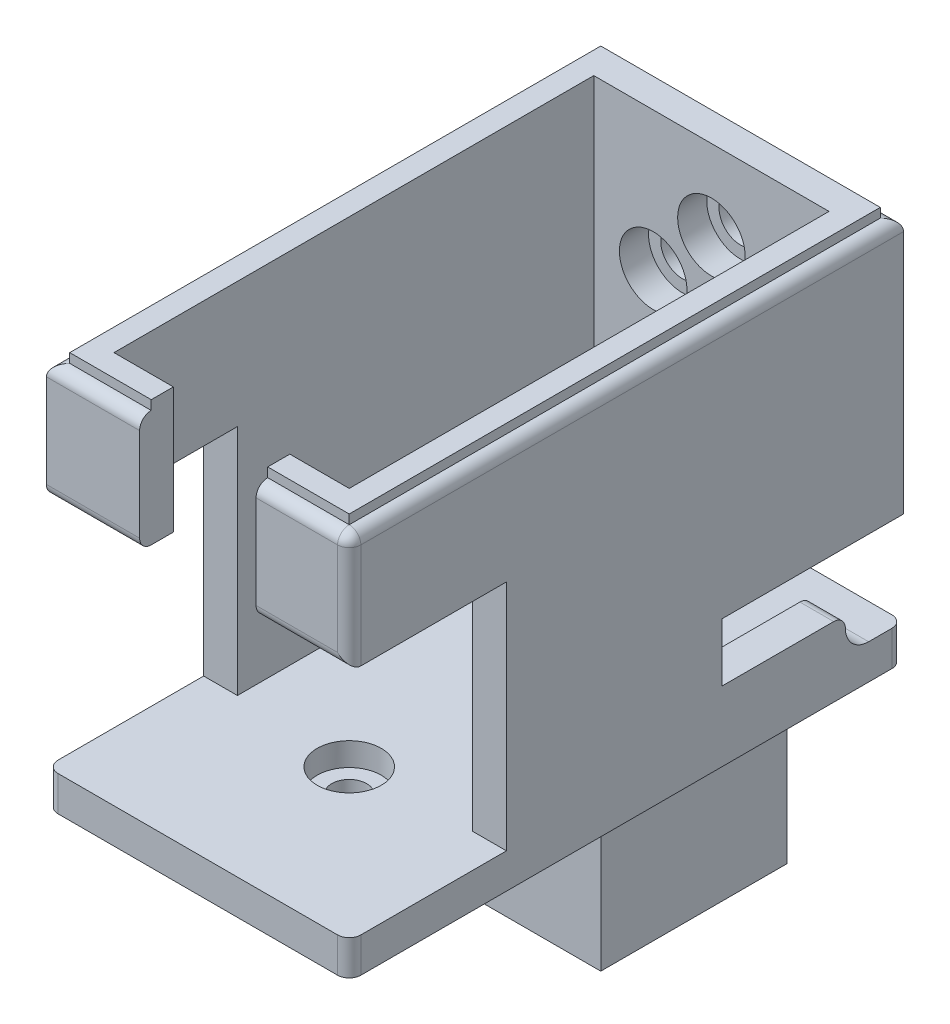
SolidWorks part; units mm, degrees
other "Markup1"
sketch "Sketch34" plane through (-13, 10, 23.5) normal (-0.1734, 0.635, 0.7528) x (0.9767, 0.2093, 0.0485)
ref_plane "Front Plane" through (0, 0, 0) normal (0, 0, 1) x (1, 0, 0)
ref_plane "Top Plane" through (0, 0, 0) normal (0, 1, 0) x (1, 0, 0)
ref_plane "Right Plane" through (0, 0, 0) normal (1, 0, 0) x (0, 0, -1)
sketch "Sketch1" plane through (0, 0, 0) normal (0, 1, 0) x (1, 0, 0)
  line L0 (5, -23.5) -> (13, -23.5)
  line L1 (-10, 20.5) -> (10, 20.5)
  line L2 (-10, 20.5) -> (-10, -20.5)
  line L3 (-10, -20.5) -> (-5, -20.5)
  line L4 (10, 20.5) -> (10, -20.5)
  line L5 (-10, 20.5) -> (10, -20.5) construction
  line L6 (-10, -20.5) -> (10, 20.5) construction
  line L7 (-13, 23.5) -> (13, 23.5)
  line L8 (-13, 23.5) -> (-13, -23.5)
  line L9 (-13, -23.5) -> (-5, -23.5)
  line L10 (13, 23.5) -> (13, -23.5)
  line L11 (-13, 23.5) -> (13, -23.5) construction
  line L12 (-13, -23.5) -> (13, 23.5) construction
  line L14 (-5, -20.5) -> (-5, -23.5)
  line L16 (5, -20.5) -> (5, -23.5)
  line L17 (5, -20.5) -> (10, -20.5)
  point P0 (0, 0)
  point P6 (0, 0)
  dimension "D1" = 20
  dimension "D2" = 41
  dimension "D3" = 3
  dimension "D4" = 3
  dimension "D5" = 5
  dimension "D6" = 5
extrude "Boss-Extrude1" add sketch "Sketch1" along normal blind 10
sketch "Sketch2" plane through (13, 0, 0) normal (1, 0, 0) x (0, 0, -1)
  line L0 (-23.5, 0) -> (23.5, 0) construction
  line L1 (-10, 0) -> (10, 0)
  line L2 (-10, 0) -> (-10, -17)
  line L3 (-10, -17) -> (10, -17)
  line L4 (10, 0) -> (10, -17)
  dimension "D1" = 10
  dimension "D2" = 10
  dimension "D3" = 17
extrude "Boss-Extrude2" add sketch "Sketch2" against normal blind 3
ref_plane "Plane1" through (0, 0, 0) normal (1, 0, 0) x (0, 0, -1)
mirror "Mirror1" about plane through (0, 0, 0) normal (1, 0, 0) of "Boss-Extrude2"
sketch "Sketch3" plane through (0, -17, 0) normal (0, -1, 0) x (1, 0, 0)
  line L1 (-13, 23.5) -> (13, 23.5)
  line L2 (-13, 23.5) -> (-13, -23.5)
  line L3 (-13, -23.5) -> (13, -23.5)
  line L4 (13, 23.5) -> (13, -23.5)
extrude "Boss-Extrude3" add sketch "Sketch3" along normal blind 3
sketch "Sketch5" plane through (0, -20, 0) normal (0, -1, 0) x (1, 0, 0)
  line L1 (10, 20.5) -> (5, 20.5) construction
  line L2 (10, 10) -> (10, -10) construction
  line L3 (-10, 10) -> (-10, -10) construction
  line L4 (-8, -4.5) -> (8, -4.5)
  line L5 (-8, -4.5) -> (-8, -8.5)
  line L6 (-8, -8.5) -> (8, -8.5)
  line L7 (8, -4.5) -> (8, -8.5)
  line L8 (-8, -12.5) -> (8, -12.5)
  line L9 (-8, -12.5) -> (-8, -16.5)
  line L10 (-8, -16.5) -> (8, -16.5)
  line L11 (8, -12.5) -> (8, -16.5)
  line L12 (-10, -10) -> (-10, -20.5) construction
  line L13 (10, -20.5) -> (10, -10) construction
  line L14 (-10, -20.5) -> (10, -20.5) construction
  circle A0 centre (0, 10.5) radius 8
  dimension "D1" = 10
  dimension "D2" = 10
  dimension "D3" = 2
  dimension "D4" = 2
  dimension "D5" = 2
  dimension "D6" = 2
  dimension "D7" = 4
  dimension "D8" = 4
  dimension "D9" = 4
  dimension "D10" = 4
extrude "Cut-Extrude1" cut sketch "Sketch5" against normal through all
sketch "Sketch6" plane through (13, 0, 0) normal (1, 0, 0) x (0, 0, -1)
  line L0 (23.5, -20) -> (23.5, 20.7) construction
  line L1 (23.5, -20) -> (-23.5422, -20) construction
  line L2 (23.5, -20) -> (23.5, 20.7) construction
  line L3 (23.5, 20.7) -> (-23.5422, 20.7) construction
  line L4 (-23.5422, -20) -> (-23.5422, 20.7) construction
  line L5 (23.5, -20) -> (23.5, 20.7) construction
  line L6 (23.5, 0.35) -> (-23.5422, 0.35) construction
  line L7 (10, -17) -> (10, 0) construction
  line L8 (23.5, 4.35) -> (29.5, 4.35)
  line L9 (23.5, 4.35) -> (23.5, -3.65)
  line L10 (23.5, -3.65) -> (29.5, -3.65)
  line L11 (29.5, 4.35) -> (29.5, -3.65)
  line L12 (23.5, 0) -> (10, 0)
  line L13 (23.5, 0) -> (23.5, -9.3)
  line L14 (23.5, -9.3) -> (10, -9.3)
  line L15 (10, 0) -> (10, -9.3)
  line M19 (10, -17) -> (10, 0)
  line M20 (10, 0) -> (23.5, 0)
  line M21 (23.5, 0) -> (23.5, 10)
  dimension "D1" = 40.7
  dimension "D2" = 4
  dimension "D3" = 4
  dimension "D4" = 6
  dimension "D5" = 5.65
extrude "Boss-Extrude4" add sketch "Sketch6" against normal blind 26 contours L11 L8 L9 L10 M21 | L14 L13 L9 M20 M19 region at (13, 0.35, -26.5) region at (13, -4.65, -16.75)
sketch "Sketch7" plane through (0, 0, 0) normal (0, 1, 0) x (1, 0, 0)
  line L1 (-10, 20.5) -> (10, 20.5)
  line L2 (-10, 20.5) -> (-10, 10)
  line L3 (-10, 10) -> (10, 10)
  line L4 (10, 20.5) -> (10, 10)
extrude "Cut-Extrude2" cut sketch "Sketch7" against normal blind 10
sketch "Sketch9" plane through (0, 4.35, 0) normal (0, 1, 0) x (1, 0, 0)
  line L0 (13, 23.5) -> (-13, 23.5) construction
  line L1 (-13, 29.5) -> (-5, 29.5)
  line L2 (-13, 29.5) -> (-13, 23.5)
  line L3 (-13, 23.5) -> (-5, 23.5)
  line L4 (-5, 29.5) -> (-5, 23.5)
  line L5 (-13, 23.5) -> (13, 23.5) construction
  line L6 (13, 29.5) -> (5, 29.5)
  line L7 (13, 29.5) -> (13, 23.5)
  line L8 (13, 23.5) -> (5, 23.5)
  line L9 (5, 29.5) -> (5, 23.5)
  dimension "D1" = 8
  dimension "D2" = 8
extrude "Cut-Extrude3" cut sketch "Sketch9" against normal blind 10
sketch "Sketch10" plane through (0, 0, -29.5) normal (0, 0, -1) x (-1, 0, 0)
  line L1 (-15, 15) -> (15, 15)
  line L2 (-15, 15) -> (-15, -15)
  line L3 (-15, -15) -> (15, -15)
  line L4 (15, 15) -> (15, -15)
  line L5 (-15, 15) -> (15, -15) construction
  line L6 (-15, -15) -> (15, 15) construction
  point P0 (0, 0)
  dimension "D1" = 30
  dimension "D2" = 30
extrude "Boss-Extrude5" add sketch "Sketch10" along normal blind 3
sketch "Sketch11" plane through (0, 0, -32.5) normal (0, 0, -1) x (-1, 0, 0)
  circle A0 centre (0, 10) radius 1.75
  circle A4 centre (10, 0) radius 1.75
  circle A5 centre (0, -10) radius 1.75
  circle A6 centre (-10, 0) radius 1.75
  point P12 (-1, 1)
  point P13 (0, 0)
  dimension "D1" = 3.5
  dimension "D3" = 0
  dimension "D4" = 4
  dimension "D5" = 10
  dimension "D6" = 10
  dimension "D2" = 10
extrude "Cut-Extrude4" cut sketch "Sketch11" against normal blind 5
sketch "Sketch12" plane through (0, -20, 0) normal (0, -1, 0) x (1, 0, 0)
  line L9 (-13, 23.5) -> (13, 23.5)
  line L10 (-13, 23.5) -> (-13, -23.5)
  line L11 (-13, -23.5) -> (13, -23.5)
  line L12 (13, 23.5) -> (13, -23.5)
  circle A0 centre (0, 10.5) radius 8
extrude "Boss-Extrude6" add sketch "Sketch12" along normal blind 3
sketch "Sketch14" plane through (0, -17, 0) normal (0, 1, 0) x (1, 0, 0)
  line L1 (-13, 23.5) -> (13, 23.5)
  line L2 (-13, 23.5) -> (-13, -23.5)
  line L3 (-13, -23.5) -> (13, -23.5)
  line L4 (13, 23.5) -> (13, -23.5)
  line L5 (-13, 10) -> (-10, 10)
  line L6 (-13, 10) -> (-13, -10)
  line L7 (-13, -10) -> (-10, -10)
  line L8 (-10, 10) -> (-10, -10)
  line L9 (10, -10) -> (13, -10)
  line L10 (10, -10) -> (10, 10)
  line L11 (10, 10) -> (13, 10)
  line L12 (13, -10) -> (13, 10)
  circle M1 centre (0, -10.5) radius 8
  line M2 (8, 4.5) -> (-8, 4.5)
  line M3 (-8, 4.5) -> (-8, 8.5)
  line M4 (-8, 8.5) -> (8, 8.5)
  line M5 (8, 8.5) -> (8, 4.5)
  line M6 (8, 12.5) -> (-8, 12.5)
  line M7 (-8, 12.5) -> (-8, 16.5)
  line M8 (-8, 16.5) -> (8, 16.5)
  line M9 (8, 16.5) -> (8, 12.5)
  line M10 (13, -10) -> (10, -10)
  line M11 (10, -10) -> (10, 10)
  line M12 (10, 10) -> (13, 10)
  line M13 (13, 10) -> (13, 23.5)
  line M14 (13, 23.5) -> (-13, 23.5)
  line M15 (-13, 23.5) -> (-13, 10)
  line M16 (-13, 10) -> (-10, 10)
  line M17 (-10, 10) -> (-10, -10)
  line M18 (-10, -10) -> (-13, -10)
  line M19 (-13, -10) -> (-13, -23.5)
  line M20 (-13, -23.5) -> (13, -23.5)
  line M21 (13, -23.5) -> (13, -10)
extrude "Cut-Extrude5" cut sketch "Sketch14" against normal blind 3 contours M21 M10 M11 M12 M13 M14 M15 M16 M17 M18 M19 M20 M5 M2 M3 M4 M9 M6 M7 M8 M1 region at (0, -17, -0.9925)
sketch "Sketch15" plane through (13, 0, 0) normal (1, 0, 0) x (0, 0, -1)
  line L0 (10, -20) -> (23.5, -20) construction
  line L1 (23.5, -17) -> (-23.5, -17)
  line L2 (23.5, -17) -> (23.5, 20.7)
  line L3 (23.5, 20.7) -> (-23.5, 20.7)
  line L4 (-23.5, -17) -> (-23.5, 20.7)
  line L5 (23.5, -23) -> (-23.5, -23) construction
  line L6 (11.2985, 20.7) -> (11.2985, -23) construction
  line L7 (11.2985, -23) -> (11.2985, -1.15) construction
  line L8 (11.2985, -1.15) -> (42.746, -1.15) construction
  line L10 (32.5, 15) -> (23.5, 15)
  line L11 (32.5, 15) -> (32.5, -15.2438)
  line L12 (32.5, -15.2438) -> (23.5, -15.2438)
  line L13 (23.5, 15) -> (23.5, -15.2438)
  line M11 (23.5, -9.3) -> (23.5, 10)
  dimension "D1" = 3
  dimension "D2" = 43.7
extrude "Cut-Extrude7" cut sketch "Sketch15" against normal through all both and the other way through all contours L12 L11 L10 L2 M11 region at (13, -0.1219, -28)
sketch "Sketch16" plane through (0, -9.3, 0) normal (0, -1, 0) x (1, 0, 0)
  line L0 (-13, 23.5) -> (-13, -23.5) construction
  line L1 (13, -23.5) -> (-13, -23.5)
  line L2 (13, -23.5) -> (13, -10)
  line L3 (13, -10) -> (-13, -10)
  line L4 (-13, -23.5) -> (-13, -10)
  line L5 (10, -10) -> (13, -10) construction
  line L7 (10, -20.5) -> (-10, -20.5)
  line L8 (10, -20.5) -> (10, -10)
  line L9 (10, -10) -> (-10, -10)
  line L10 (-10, -20.5) -> (-10, -10)
  line M2 (10, -20.5) -> (-10, -20.5)
  line M3 (-10, -20.5) -> (-10, -10)
  line M4 (-10, -10) -> (-13, -10)
  line M5 (-13, -10) -> (-13, -23.5)
  line M6 (-13, -23.5) -> (13, -23.5)
  line M7 (13, -23.5) -> (13, -10)
  line M8 (13, -10) -> (10, -10)
  line M9 (10, -10) -> (10, -20.5)
  dimension "D1" = 0
extrude "Boss-Extrude7" add sketch "Sketch16" along normal blind 10.7 contours M9 M2 M3 M4 M5 M6 M7 M8 region at (0, -9.3, -23.207)
sketch "Sketch18" plane through (13, 0, 0) normal (1, 0, 0) x (0, 0, -1)
  line L0 (23.5, 10) -> (23.5, -23) construction
  line L1 (23.5, -17) -> (8.5, -17)
  line L2 (23.5, -17) -> (23.5, -12)
  line L3 (23.5, -12) -> (8.5, -12)
  line L4 (8.5, -17) -> (8.5, -12)
  line L5 (-23.5, -20) -> (-10, -20) construction
  dimension "D1" = 3
  dimension "D2" = 15
  dimension "D3" = 5
extrude "Cut-Extrude8" cut sketch "Sketch18" against normal blind 10
mirror "Mirror2" about plane through (0, 0, 0) normal (1, 0, 0) of "Cut-Extrude8"
sketch "Sketch21" plane through (0, 0, -23.5) normal (0, 0, -1) x (-1, 0, 0)
  line L0 (0, 20.7) -> (0, -23) construction
  line L1 (-13, -23) -> (13, -23)
  line L2 (-13, -23) -> (-13, 20.7)
  line L3 (-13, 20.7) -> (13, 20.7)
  line L4 (13, -23) -> (13, 20.7)
  line L5 (0, -23) -> (0, -1.15) construction
  line L6 (0, -1.15) -> (13, -1.15) construction
  circle A0 centre (0, 3.85) radius 1.85
  circle A1 centre (5, -1.15) radius 1.85
  circle A2 centre (0, -6.15) radius 1.85
  circle A3 centre (-5, -1.15) radius 1.85
  point P19 (0, -1.15)
  dimension "D2" = 5
  dimension "D3" = 3.7
  dimension "D5" = 5
  dimension "D6" = 5
  dimension "D1" = 43.7
  dimension "D4" = 4
extrude "Cut-Extrude9" cut sketch "Sketch21" against normal blind 5 contours A3 | A0 | A1 | A2 region at (0, 3.85, -23.5) region at (-5, -1.15, -23.5) region at (0, -6.15, -23.5) region at (5, -1.15, -23.5)
sketch "Sketch22" plane through (0, 0, -20.5) normal (0, 0, 1) x (1, 0, 0)
  line L0 (0, 3.85) -> (0, -6.15) construction
  line L1 (0, -6.15) -> (0, -1.15) construction
  line L2 (0, -1.15) -> (5, -1.15) construction
  circle A0 centre (0, 3.85) radius 2.9
  circle A1 centre (5, -1.15) radius 2.9
  circle A2 centre (0, -6.15) radius 2.9
  circle A3 centre (-5, -1.15) radius 2.9
  point P17 (0, -1.15)
  dimension "D1" = 5.8
  dimension "D2" = 4
extrude "Cut-Extrude10" cut sketch "Sketch22" against normal blind 2.6
sketch "Sketch23" plane through (0, 0, -23.5) normal (0, 0, -1) x (-1, 0, 0)
  line L0 (-3, -17) -> (-13, -17)
  line L1 (-13, 10) -> (13, 10)
  line L2 (-13, 10) -> (-13, -12)
  line L3 (-13, -12) -> (-3, -12)
  line L4 (13, 10) -> (13, -12)
  line L10 (-3, -12) -> (-3, -17)
  line L12 (3, -12) -> (3, -17)
  line L13 (13, -17) -> (3, -17)
  line L14 (13, -17) -> (13, -23)
  line L15 (13, -23) -> (-13, -23)
  line L16 (-13, -17) -> (-13, -23)
  line L17 (3, -12) -> (13, -12)
  circle A0 centre (0, 3.85) radius 1.75
  circle A1 centre (0, -6.15) radius 1.75
  circle A2 centre (5, -1.15) radius 1.75
  circle A3 centre (-5, -1.15) radius 1.75
  circle M1 centre (-5, -1.15) radius 1.85
  circle M2 centre (0, 3.85) radius 1.85
  circle M3 centre (5, -1.15) radius 1.85
  circle M4 centre (0, -6.15) radius 1.85
  line M5 (3, -12) -> (13, -12)
  line M6 (13, -12) -> (13, 10)
  line M7 (13, 10) -> (-13, 10)
  line M8 (-13, 10) -> (-13, -12)
  line M9 (-13, -12) -> (-3, -12)
extrude "Boss-Extrude11" add sketch "Sketch23" along normal blind 0.6 contours L3 M9 M5 M6 M7 M8 M2 M4 M3 M1 region at (2.5799, -14.5, -23.5)
sketch "Sketch24" plane through (0, 0, -24.1) normal (0, 0, -1) x (-1, 0, 0)
  line L5 (5, -1.15) -> (0, -1.15) construction
  line L7 (0, 3.85) -> (0, -6.15) construction
  line L8 (-4.5, 6.35) -> (4.5, 6.35)
  line L9 (-13, 6.35) -> (-13, -8.65)
  line L10 (-4.5, -8.65) -> (4.5, -8.65)
  line L11 (13, 6.35) -> (13, -8.65)
  line L12 (-13, 6.35) -> (13, -8.65) construction
  line L13 (-13, -8.65) -> (13, 6.35) construction
  line L15 (-7.5, 6.35) -> (7.5, 6.35)
  line L16 (-7.5, 3.35) -> (-7.5, -5.65)
  line L17 (-7.5, -8.65) -> (7.5, -8.65)
  line L18 (7.5, 3.35) -> (7.5, -5.65)
  line L19 (-7.5, 6.35) -> (7.5, -8.65) construction
  line L20 (-7.5, -8.65) -> (7.5, 6.35) construction
  circle A0 centre (0, 3.85) radius 1.75
  circle A1 centre (0, -6.15) radius 1.75
  circle A2 centre (5, -1.15) radius 1.75
  circle A3 centre (-5, -1.15) radius 1.75
  arc A4 (7.5, 3.35) -> (4.5, 6.35) centre (4.5, 3.35) ccw
  arc A5 (7.5, -5.65) -> (4.5, -8.65) centre (4.5, -5.65) cw
  arc A6 (-4.5, -8.65) -> (-7.5, -5.65) centre (-4.5, -5.65) cw
  arc A7 (-7.5, 3.35) -> (-4.5, 6.35) centre (-4.5, 3.35) cw
  point P0 (0, -0.7463)
  circle M11 centre (0, 3.85) radius 1.85
  circle M12 centre (0, -6.15) radius 1.85
  circle M25 centre (5, -1.15) radius 1.85
  circle M26 centre (-5, -1.15) radius 1.85
  dimension "D3" = 3
  dimension "D2" = 15
extrude "Boss-Extrude12" add sketch "Sketch24" along normal blind 4 contours A7 L16 A6 L10 A5 L18 A4 L8 M12 M25 M26 M11 region at (0, -1.15, -24.1)
sketch "Sketch25" plane through (0, 0, -24.1) normal (0, 0, -1) x (-1, 0, 0)
  line L1 (-10, -17) -> (-3, -17)
  line L2 (-10, -17) -> (-10, -20)
  line L3 (-10, -20) -> (-3, -20)
  line L4 (-3, -17) -> (-3, -20)
  line L5 (3, -17) -> (10, -17)
  line L6 (3, -17) -> (3, -20)
  line L7 (3, -20) -> (10, -20)
  line L8 (10, -17) -> (10, -20)
  dimension "D1" = 3
  dimension "D2" = 3
extrude "Cut-Extrude11" cut sketch "Sketch25" against normal blind 5
sketch "Sketch26" plane through (0, 10, 0) normal (0, 1, 0) x (1, 0, 0)
  line L0 (-10, 20.5) -> (10, 20.5) construction
  line L1 (-10.1, 20.6) -> (10.1, 20.6)
  line L2 (-10.1, 20.6) -> (-10.1, -20.6)
  line L3 (-10.1, -20.6) -> (10.1, -20.6)
  line L4 (10.1, 20.6) -> (10.1, -20.6)
  line L5 (-10, -20.5) -> (-10, 20.5) construction
  line L6 (10, -10) -> (10, 24.1) construction
  line L7 (-5, -20.5) -> (-10, -20.5) construction
  dimension "D1" = 0.1
  dimension "D2" = 0.1
  dimension "D3" = 0.1
  dimension "D4" = 0.1
extrude "Cut-Extrude12" cut sketch "Sketch26" against normal blind 30
sketch "Sketch27" plane through (0, 0, -24.1) normal (0, 0, -1) x (-1, 0, 0)
  line L0 (0, -23) -> (0, -16.7281) construction
  line L1 (-13, -23) -> (13, -23) construction
  line L2 (-10, -20) -> (-10.1, -20)
  line L3 (10, -17) -> (10.1, -17)
  line L4 (10, -17) -> (10, -20)
  line L5 (10, -20) -> (10.1, -20)
  line L6 (10.1, -17) -> (10.1, -20)
  line L7 (-10.1, -17) -> (-10.1, -20)
  line L8 (-10, -17) -> (-10.1, -17)
  line L9 (-10, -17) -> (-10, -20)
extrude "Cut-Extrude13" cut sketch "Sketch27" against normal through all
sketch "Sketch28" plane through (0, -23, 0) normal (0, -1, 0) x (1, 0, 0)
  line L0 (0, 10.5) -> (0, 23.5) construction
  line L1 (13, 23.5) -> (-13, 23.5) construction
  line L2 (0, -24.1) -> (0, -11.1) construction
  line L3 (4.5, -24.1) -> (-4.5, -24.1) construction
  line L4 (0, 10.5) -> (0, -11.1) construction
  circle A0 centre (0, -11.1) radius 8
  dimension "D2" = 16
  dimension "D1" = 13
extrude "Cut-Extrude14" cut sketch "Sketch28" against normal through all
sketch "Sketch29" plane through (0, 0, -24.1) normal (0, 0, -1) x (-1, 0, 0)
  line L0 (-13, -17) -> (-13, -23) construction
  line L1 (-10.1, -17) -> (-13, -17)
  line L2 (-10.1, -17) -> (-10.1, -20)
  line L3 (-10.1, -20) -> (-13, -20)
  line L4 (-13, -17) -> (-13, -20)
  line L6 (10.1, -20) -> (13, -20)
  line L7 (10.1, -20) -> (10.1, -17)
  line L8 (10.1, -17) -> (13, -17)
  line L9 (13, -20) -> (13, -17)
extrude "Cut-Extrude15" cut sketch "Sketch29" against normal blind 5
fillet "Fillet1" radius 2 2 edges at (-3, -20, -22.35) (3, -20, -22.35)
fillet "Fillet2" radius 2 2 edges at (-11.55, -20, -19.1) (11.55, -20, -19.1)
fillet "Fillet3" radius 1 14 edges at (-11.55, -17, -19.1) (11.55, -17, -19.1) (-13, -21.5, -24.1) (13, -21.5, -24.1) (-13, -21.5, 23.5) (13, -21.5, 23.5) (0, 10, -24.1) (-13, 10, -0.3) (-9, 0, 23.5) (-9, 10, 23.5) (9, 0, 23.5) (9, 10, 23.5) (13, 10, -0.3) (13, 5, 23.5)
sketch "Sketch35" plane through (0, -20, 0) normal (0, 1, 0) x (1, 0, 0)
  circle A0 centre (0, -10.5) radius 8
  circle A1 centre (0, -10.5) radius 2.5
  dimension "D1" = 5
extrude "Boss-Extrude13" add sketch "Sketch35" against normal blind 5
sketch "Sketch36" plane through (0, 10, 0) normal (0, 1, 0) x (1, 0, 0)
  line L1 (-12, 23.1) -> (12, 23.1)
  line L2 (-12, 23.1) -> (-12, -22.5)
  line L3 (-12, -22.5) -> (12, -22.5)
  line L4 (12, 23.1) -> (12, -22.5)
  line L5 (10.1, -20.6) -> (-10.1, -20.6)
  line L6 (10.1, -20.6) -> (10.1, 20.6)
  line L7 (10.1, 20.6) -> (-10.1, 20.6)
  line L8 (-10.1, -20.6) -> (-10.1, 20.6)
  line L9 (-5, -22.5) -> (5, -22.5)
  line L10 (-5, -22.5) -> (-5, -20.6)
  line L11 (-5, -20.6) -> (5, -20.6)
  line L12 (5, -22.5) -> (5, -20.6)
  line M1 (-12, 23.1) -> (-12, -22.5)
  line M2 (-12, -22.5) -> (-5, -22.5)
  line M3 (-5, -22.5) -> (-5, -20.6)
  line M4 (-5, -20.6) -> (-10.1, -20.6)
  line M5 (-10.1, -20.6) -> (-10.1, 20.6)
  line M6 (-10.1, 20.6) -> (10.1, 20.6)
  line M7 (10.1, 20.6) -> (10.1, -20.6)
  line M8 (10.1, -20.6) -> (5, -20.6)
  line M9 (5, -20.6) -> (5, -22.5)
  line M10 (5, -22.5) -> (12, -22.5)
  line M11 (12, -22.5) -> (12, 23.1)
  line M12 (12, 23.1) -> (-12, 23.1)
extrude "Boss-Extrude14" add sketch "Sketch36" along normal blind 0.8 contours M12 M1 M2 M3 M4 M5 M6 M7 M8 M9 M10 M11 region at (0, 10, -22.5847)
sketch "Sketch38" plane through (0, -25, 0) normal (0, -1, 0) x (1, 0, 0)
  circle A0 centre (0, 10.5) radius 2.5
  circle A1 centre (0, 10.5) radius 2.55
  dimension "D1" = 5.1
extrude "Cut-Extrude16" cut sketch "Sketch38" against normal blind 2
sketch "Sketch39" plane through (0, -23, 0) normal (0, -1, 0) x (1, 0, 0)
  circle A0 centre (0, 10.5) radius 2.55
  circle A1 centre (0, 10.5) radius 1.25
  dimension "D1" = 2.5
extrude "Boss-Extrude15" add sketch "Sketch39" against normal blind 1
sketch "Sketch40" plane through (0, -25, 0) normal (0, -1, 0) x (1, 0, 0)
  circle A0 centre (0, 10.5) radius 8
  circle A1 centre (0, 10.5) radius 6.5
  dimension "D1" = 13
  dimension "D2" = 16
extrude "Cut-Extrude17" cut sketch "Sketch40" against normal blind 4
sketch "Sketch41" plane through (0, -23, 0) normal (0, -1, 0) x (1, 0, 0)
  line L0 (0, -3.1) -> (0, -19.1) construction
  line L3 (-8, -3.1) -> (8, -3.1)
  line L4 (-8, -3.1) -> (-8, -19.1)
  line L5 (-8, -19.1) -> (8, -19.1)
  line L6 (8, -3.1) -> (8, -19.1)
  line L7 (-8, -3.1) -> (8, -19.1) construction
  line L8 (-8, -19.1) -> (8, -3.1) construction
  circle A0 centre (0, -11.1) radius 8 construction
  point P5 (0, -11.1)
  dimension "D1" = 16
  dimension "D2" = 16
extrude "Boss-Extrude16" add sketch "Sketch41" along normal blind 15 and the other way blind 3
fillet "Fillet4" radius 5 1 edges at (0, -23, -3.1)
fillet "Fillet5" radius 3 1 edges at (0, -23, -19.1)
sketch "Sketch42" plane through (7.5, 0, 0) normal (1, 0, 0) x (0, 0, -1)
  line L1 (28.1, 6.35) -> (24.1, 6.35)
  line L2 (28.1, 6.35) -> (28.1, -8.65)
  line L3 (28.1, -8.65) -> (24.1, -8.65)
  line L4 (24.1, 6.35) -> (24.1, -8.65)
extrude "Cut-Extrude18" cut sketch "Sketch42" against normal through all
sketch "Sketch43" plane through (0, -23, 0) normal (0, -1, 0) x (1, 0, 0)
  circle A0 centre (0, 10.5) radius 1.5
  dimension "D1" = 3
extrude "Cut-Extrude19" cut sketch "Sketch43" against normal through all
sketch "Sketch44" plane through (0, -20, 0) normal (0, 1, 0) x (1, 0, 0)
  circle A0 centre (0, -10.5) radius 2.75
  dimension "D1" = 5.5
extrude "Cut-Extrude20" cut sketch "Sketch44" along direction (0, -1, 0) on the side against the normal up to surface (2 mm away) up to face at (0, -22, 9)
